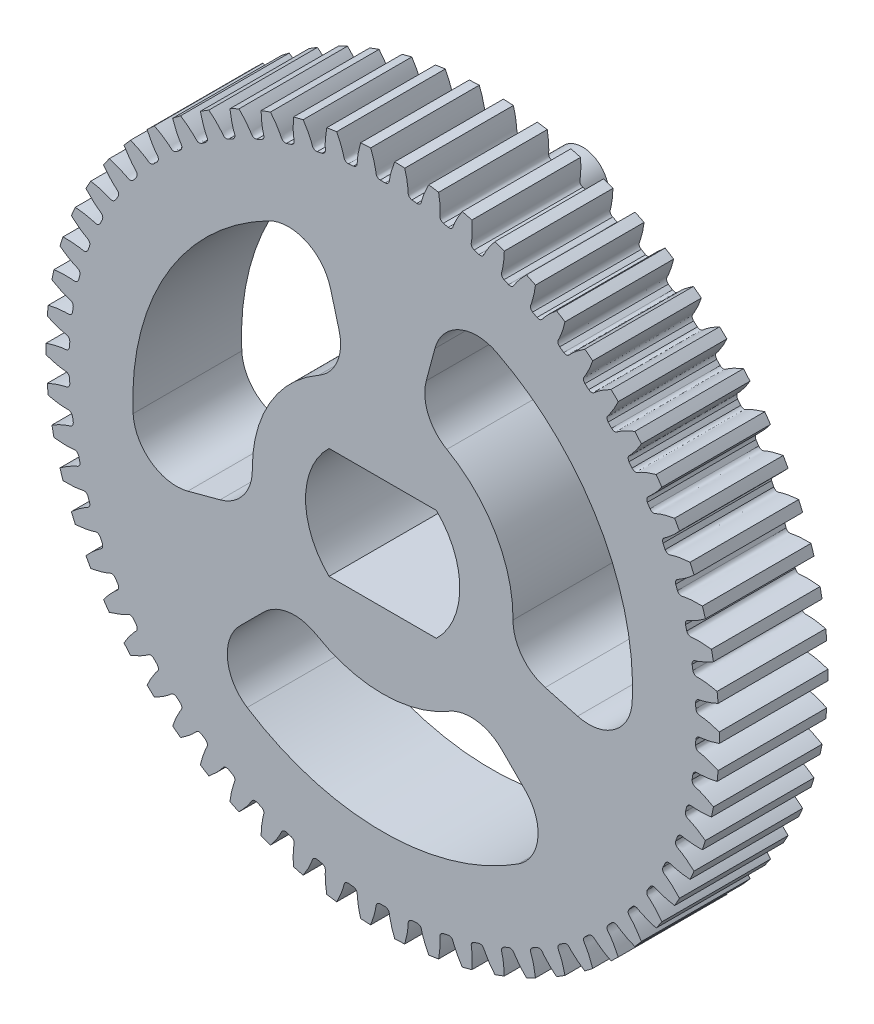
SolidWorks part; units mm, degrees
ref_plane "前视基准面" through (0, 0, 0) normal (0, 0, 1) x (1, 0, 0)
ref_plane "上视基准面" through (0, 0, 0) normal (0, 1, 0) x (1, 0, 0)
ref_plane "右视基准面" through (0, 0, 0) normal (1, 0, 0) x (0, 0, -1)
sketch "草图1" plane through (0, 0, 0) normal (0, 0, 1) x (1, 0, 0)
  circle A0 centre (0, 0) radius 15.4962
extrude "凸台-拉伸1" add sketch "草图1" along normal blind 5
ref_axis "基准轴1" through (0, 0, 5) along (0, 0, -1)
sketch "草图2" plane through (0, 0, 0) normal (0, 0, 1) x (1, 0, 0)
  line L0 (0, 0) -> (0, 15.4962) construction
  circle A0 centre (0, 0) radius 15.4962 construction
  arc A1 (0.1151, 14.4252) -> (-0.1151, 14.4252) centre (0, 0) ccw
  arc A2 (1.8451, 17.5425) -> (-1.8451, 17.5425) centre (0, 0) ccw
  spline S0 degree 3 poles (0.1151, 14.4252) (0.3005, 14.4547) (0.3019, 14.578) (0.3231, 14.712) (0.3308, 14.756) (0.3406, 14.8055) (0.3526, 14.8604) (0.367, 14.9208) (0.3841, 14.9865) (0.4041, 15.0575) (0.4272, 15.1337) (0.4536, 15.2149) (0.4835, 15.301) (0.5172, 15.392) (0.5548, 15.4878) (0.5966, 15.5881) (0.6427, 15.693) (0.6934, 15.8022) (0.7487, 15.9155) (0.809, 16.033) (0.8744, 16.1543) (0.9451, 16.2794) (1.0212, 16.408) (1.103, 16.5401) (1.1905, 16.6754) (1.284, 16.8137) (1.3836, 16.9549) (1.4894, 17.0988) (1.6414, 17.297) (1.7618, 17.4444) (1.8451, 17.5425) knots 0 0 0 0 0.089701 0.100437 0.112786 0.126748 0.142323 0.15951 0.178311 0.198725 0.220751 0.244391 0.269643 0.296509 0.324987 0.355078 0.386782 0.4201 0.45503 0.491573 0.529729 0.569498 0.610879 0.653874 0.698482 0.744703 0.792536 0.841983 0.893042 1 1 1 1
  spline S1 degree 3 poles (-0.1151, 14.4252) (-0.3005, 14.4547) (-0.3019, 14.578) (-0.3231, 14.712) (-0.3308, 14.756) (-0.3406, 14.8055) (-0.3526, 14.8604) (-0.367, 14.9208) (-0.3841, 14.9865) (-0.4041, 15.0575) (-0.4272, 15.1337) (-0.4536, 15.2149) (-0.4835, 15.301) (-0.5172, 15.392) (-0.5548, 15.4878) (-0.5966, 15.5881) (-0.6427, 15.693) (-0.6934, 15.8022) (-0.7487, 15.9155) (-0.809, 16.033) (-0.8744, 16.1543) (-0.9451, 16.2794) (-1.0212, 16.408) (-1.103, 16.5401) (-1.1905, 16.6754) (-1.284, 16.8137) (-1.3836, 16.9549) (-1.4894, 17.0988) (-1.6414, 17.297) (-1.7618, 17.4444) (-1.8451, 17.5425) knots 0 0 0 0 0.089701 0.100437 0.112786 0.126748 0.142323 0.15951 0.178311 0.198725 0.220751 0.244391 0.269643 0.296509 0.324987 0.355078 0.386782 0.4201 0.45503 0.491573 0.529729 0.569498 0.610879 0.653874 0.698482 0.744703 0.792536 0.841983 0.893042 1 1 1 1
extrude "切除-拉伸1" cut sketch "草图2" along normal through all
pattern_circular "阵列(圆周)1" count 62 over 360 about axis through (0, 0, 5) along (0, 0, -1) of "切除-拉伸1"
sketch "草图6" plane through (0, 0, 0) normal (0, 0, -1) x (-1, 0, 0)
  circle A0 centre (0, 0) radius 10 construction
  circle A1 centre (0, 10) radius 1.2
  dimension "D1" = 20
  dimension "D2" = 2.4
extrude "凸台-拉伸2" add sketch "草图6" along normal blind 4.2
sketch "草图8" plane through (0, 0, 0) normal (0, 0, -1) x (-1, 0, 0)
  circle A0 centre (0, 0) radius 6
  dimension "D1" = 12
extrude "凸台-拉伸3" add sketch "草图8" along normal blind 0.8
pattern_circular "阵列(圆周)4" count 3 over 360 about axis through (0, 0, -0.8) along (0, 0, 1) of "凸台-拉伸2" reverse direction yes
sketch "草图9" plane through (0, 0, -0.8) normal (0, 0, -1) x (-1, 0, 0)
  line L1 (-7.1549, 2.55) -> (7.1549, 2.55)
  line L2 (-7.1549, 2.55) -> (-7.1549, -2.55)
  line L3 (-7.1549, -2.55) -> (7.1549, -2.55)
  line L4 (7.1549, 2.55) -> (7.1549, -2.55)
  line L5 (-7.1549, 2.55) -> (7.1549, -2.55) construction
  line L6 (-7.1549, -2.55) -> (7.1549, 2.55) construction
  circle A0 centre (0, 0) radius 3.55
  dimension "D1" = 7.1
  dimension "D2" = 5.1
extrude "切除-拉伸5" cut sketch "草图9" against normal blind 13 contours L1 A0 L3 region at (0, 0, -0.8)
sketch "草图10" plane through (0, 0, 0) normal (0, 0, -1) x (-1, 0, 0)
  line L0 (0, 0) -> (-8.1317, -8.1317)
  line L1 (0, 0) -> (0, -11.5) construction
  line L2 (0, 0) -> (8.1317, -8.1317)
  circle A0 centre (0, 0) radius 11.5
  circle A1 centre (0, 0) radius 6
  dimension "D1" = 23
  dimension "D2" = 12
  dimension "D3" = 90
extrude "切除-拉伸6" cut sketch "草图10" against normal blind 10 contours L1 A1 L0 A0 | A1 L1 A0 L2 region at (3.3705, -8.1371, 0) region at (-3.3705, -8.1371, 0)
fillet "圆角1" radius 2 4 edges at (-4.2426, -4.2426, 2.5) (4.2426, -4.2426, 2.5) (8.1317, -8.1317, 2.5) (-8.1317, -8.1317, 2.5)
pattern_circular "阵列(圆周)5" count 3 over 360 about axis through (0, 0, -0.8) along (0, 0, 1) of "圆角1", "切除-拉伸6" reverse direction yes
sketch "草图11" plane through (0, 0, 0) normal (0, 0, -1) x (-1, 0, 0)
  circle A0 centre (-8.6603, -5) radius 2
  circle A1 centre (8.6603, -5) radius 2
  circle A2 centre (0, 10) radius 2.25
  dimension "D1" = 4
  dimension "D2" = 4
  dimension "D3" = 4.5
extrude "凸台-拉伸5" add sketch "草图11" along normal blind 1
sketch "草图12" plane through (0, 0, 0) normal (0, 0, -1) x (-1, 0, 0)
  circle A0 centre (0, 0) radius 15 construction
  dimension "D1" = 30
